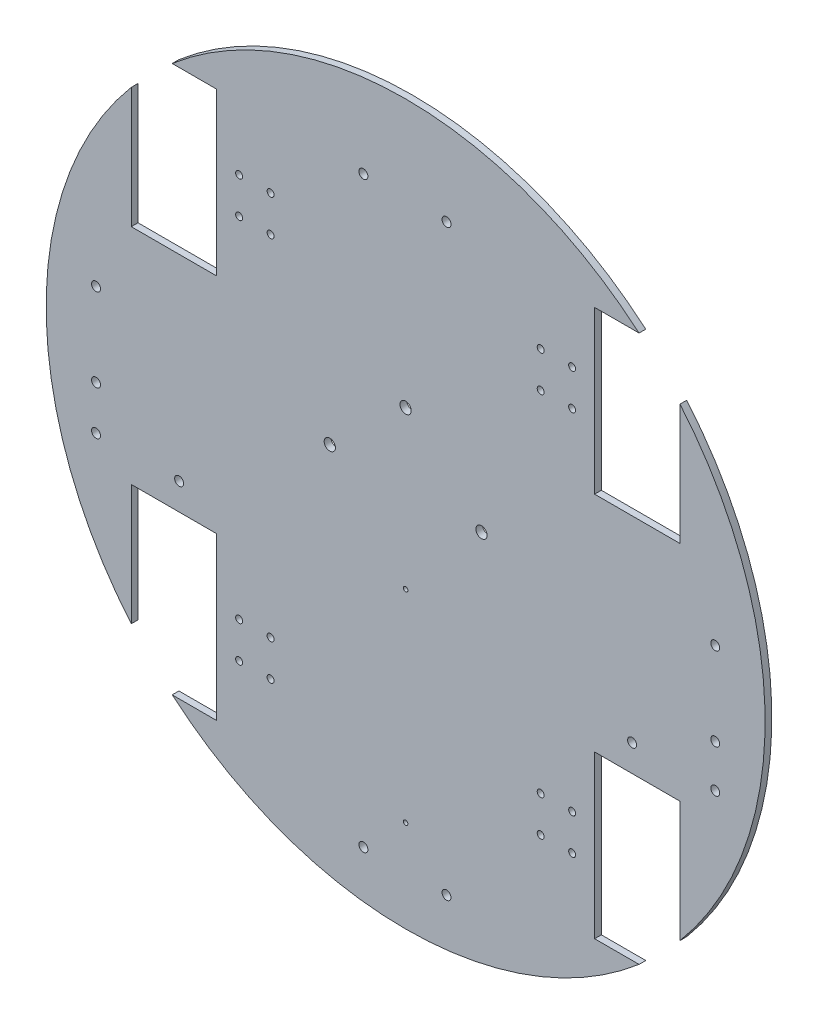
SolidWorks part; units mm, degrees
ref_plane "Front" through (0, 0, 0) normal (0, 0, 1) x (1, 0, 0)
ref_plane "Top" through (0, 0, 0) normal (0, 1, 0) x (1, 0, 0)
ref_plane "Right" through (0, 0, 0) normal (1, 0, 0) x (0, 0, -1)
ref_axis "基准轴1" through (0, -50, 0) along (0, 1, 0)
sketch "草图1" plane through (0, 0, 0) normal (0, 0, 1) x (1, 0, 0)
  line L0 (-122.1121, -103.3858) -> (-122.1121, -49.6748)
  line L1 (-122.1121, -49.6748) -> (-84.1121, -49.6748)
  line L2 (-84.1121, -49.6748) -> (-84.1121, -121.6748)
  line L3 (-84.1121, -121.6748) -> (-103.9001, -121.6748)
  line L4 (122.1121, 103.3858) -> (122.1121, 49.6748)
  line L5 (122.1121, 49.6748) -> (84.1121, 49.6748)
  line L6 (84.1121, 49.6748) -> (84.1121, 121.6748)
  line L7 (84.1121, 121.6748) -> (103.9001, 121.6748)
  line L9 (84.1121, -121.6748) -> (103.9001, -121.6748)
  line L10 (84.1121, -49.6748) -> (84.1121, -121.6748)
  line L11 (122.1121, -49.6748) -> (84.1121, -49.6748)
  line L12 (122.1121, -103.3858) -> (122.1121, -49.6748)
  line L13 (-84.1121, 121.6748) -> (-103.9001, 121.6748)
  line L14 (-84.1121, 49.6748) -> (-84.1121, 121.6748)
  line L15 (-122.1121, 49.6748) -> (-84.1121, 49.6748)
  line L16 (-122.1121, 103.3858) -> (-122.1121, 49.6748)
  arc A4 (103.9001, 121.6748) -> (-103.9001, 121.6748) centre (0, 0) ccw
  circle A6 centre (137.7997, 18.1958) radius 2
  circle A7 centre (137.7997, -18.8042) radius 2
  circle A8 centre (18.1958, -137.7997) radius 2
  circle A9 centre (-18.8042, -137.7997) radius 2
  circle A10 centre (-137.7997, -18.1958) radius 2
  circle A11 centre (-137.7997, 18.8042) radius 2
  arc A25 (-103.9001, -121.6748) -> (103.9001, -121.6748) centre (0, 0) ccw
  circle A30 centre (-60.1121, 93.6748) radius 1.55
  circle A31 centre (-60.1121, 77.6748) radius 1.55
  circle A32 centre (-74.1121, 93.6748) radius 1.55
  circle A33 centre (-74.1121, 77.6748) radius 1.55
  arc A34 (-122.1121, 103.3858) -> (-122.1121, -103.3858) centre (0, 0) ccw
  arc A35 (122.1121, -103.3858) -> (122.1121, 103.3858) centre (0, 0) ccw
  circle A36 centre (0, -119) radius 1
  circle A37 centre (0, -29) radius 1
  circle A38 centre (-33.75, 9.85) radius 2.5
  circle A39 centre (33.75, 9.85) radius 2.5
  circle A40 centre (0, 41) radius 2.5
  circle A41 centre (100.7997, -37.7219) radius 2
  circle A42 centre (137.7997, -37.7344) radius 2
  circle A43 centre (-137.7997, -37.7344) radius 2
  circle A44 centre (-100.7997, -37.7219) radius 2
  circle A45 centre (-18.8042, 121.6748) radius 2
  circle A46 centre (18.1958, 121.6748) radius 2
  circle A51 centre (74.1121, 77.6748) radius 1.55
  circle A52 centre (74.1121, 93.6748) radius 1.55
  circle A53 centre (60.1121, 77.6748) radius 1.55
  circle A54 centre (60.1121, 93.6748) radius 1.55
  circle A55 centre (60.1121, -93.6748) radius 1.55
  circle A56 centre (60.1121, -77.6748) radius 1.55
  circle A57 centre (74.1121, -93.6748) radius 1.55
  circle A58 centre (74.1121, -77.6748) radius 1.55
  circle A59 centre (-74.1121, -77.6748) radius 1.55
  circle A60 centre (-74.1121, -93.6748) radius 1.55
  circle A61 centre (-60.1121, -77.6748) radius 1.55
  circle A62 centre (-60.1121, -93.6748) radius 1.55
  point P22 (0, 0)
  point P45 (0, 0)
  dimension "D1" = 3
  dimension "D8" = 90
  dimension "D9" = 29
  dimension "D10" = 37
  dimension "D7" = 2
extrude "凸台-拉伸1" add sketch "草图1" along normal blind 3
